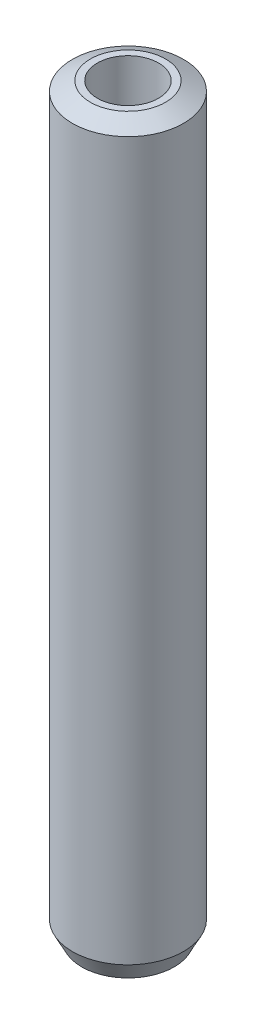
SolidWorks part; units mm, degrees
ref_plane "Front Plane" through (0, 0, 0) normal (0, 0, 1) x (1, 0, 0)
ref_plane "Top Plane" through (0, 0, 0) normal (0, 1, 0) x (1, 0, 0)
ref_plane "Right Plane" through (0, 0, 0) normal (1, 0, 0) x (0, 0, -1)
sketch "Sketch1" plane through (0, 0, 0) normal (0, 1, 0) x (1, 0, 0)
  circle A0 centre (0, 0) radius 22.5
  dimension "SHAFT_OD" = 45
extrude "Boss-Extrude1" add sketch "Sketch1" along normal blind 301.5571
sketch "Sketch2" plane through (0, 0, 0) normal (0, 1, 0) x (1, 0, 0)
  circle A0 centre (0, 0) radius 12.3939
  dimension "BORE_D" = 24.7878
extrude "Cut-Extrude1" cut sketch "Sketch2" along normal through all
chamfer "Chamfer1" distance 3.7619 angle 62.673 2 edges at (0, 301.5571, 22.5) (0, 0, 22.5) first distance on face at (0, 301.5571, 22.5) first distance on face at (0, 0, 12.3939)
